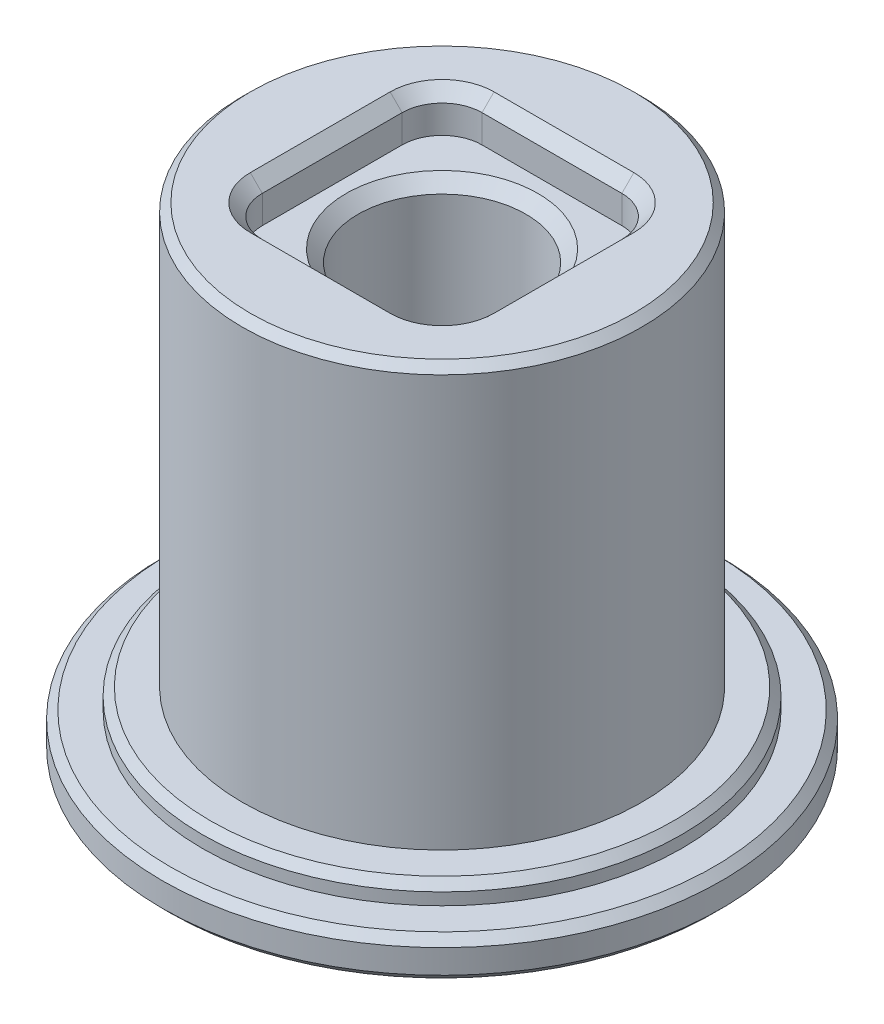
SolidWorks part; units mm, degrees
material "보통 탄소강"
ref_plane "정면" through (0, 0, 0) normal (0, 0, 1) x (1, 0, 0)
ref_plane "윗면" through (0, 0, 0) normal (0, 1, 0) x (1, 0, 0)
ref_plane "우측면" through (0, 0, 0) normal (1, 0, 0) x (0, 0, -1)
sketch "스케치1" plane through (0, 0, 0) normal (0, 1, 0) x (1, 0, 0)
  line L1 (-2.75, -2.75) -> (2.75, -2.75)
  line L2 (-2.75, -2.75) -> (-2.75, 2.75)
  line L3 (-2.75, 2.75) -> (2.75, 2.75)
  line L4 (2.75, -2.75) -> (2.75, 2.75)
  line L5 (-2.75, -2.75) -> (2.75, 2.75) construction
  line L6 (-2.75, 2.75) -> (2.75, -2.75) construction
  circle A0 centre (0, 0) radius 7
  circle A1 centre (0, 0) radius 6
  circle A2 centre (0, 0) radius 5
  circle A3 centre (0, 0) radius 4.25
  circle A5 centre (0, 0) radius 2.1
  dimension "D1" = 14
  dimension "D2" = 12
  dimension "D3" = 10
  dimension "D4" = 8.5
  dimension "D5" = 5.5
  dimension "D6" = 4.2
  dimension "D7" = 5.5
extrude "보스-돌출1" add sketch "스케치1" along normal blind 1 contours A0 A1 region at (-6.802, 0, 0)
extrude "보스-돌출2" add sketch "스케치1<4>" along normal blind 1.5 contours A1 A2 region at (-5.8303, 0, 0)
sketch "스케치1<4>" plane through (0, 0, 0) normal (0, 1, 0) x (1, 0, 0) same geometry as "스케치1"
extrude "보스-돌출3" add sketch "스케치1<5>" along normal blind 12 contours A2 A3 region at (-4.8586, 0, 0)
sketch "스케치1<5>" plane through (0, 0, 0) normal (0, 1, 0) x (1, 0, 0) same geometry as "스케치1"
extrude "보스-돌출4" add sketch "스케치1<6>" along normal blind 7 from offset 5 contours A3 region at (-4.1298, 0, 0)
sketch "스케치1<6>" plane through (0, 0, 0) normal (0, 1, 0) x (1, 0, 0) same geometry as "스케치1"
extrude "보스-돌출5" add sketch "스케치1<7>" along normal blind 6 from offset 5 contours A5 region at (-2.6722, 0, 0)
sketch "스케치1<7>" plane through (0, 0, 0) normal (0, 1, 0) x (1, 0, 0) same geometry as "스케치1"
fillet "필렛1" radius 1 4 edges at (2.75, 11.5, 2.75) (-2.75, 11.5, 2.75) (2.75, 11.5, -2.75) (-2.75, 11.5, -2.75)
chamfer "모따기1" distance 0.2 angle 45 4 edges at (0, 12, 5) (0, 1, 7) (0, 0, 7) (0, 1.5, 6)
chamfer "모따기2" distance 0.3 angle 45 1 edges at (0, 0, 4.25)
chamfer "모따기3" distance 0.3 angle 45 9 edges at (0, 11, 2.1) (0, 12, 2.75) (2.75, 12, 0) (-2.75, 12, 0) (0, 12, -2.75) (-2.4571, 12, 2.4571) (2.4571, 12, 2.4571) (-2.4571, 12, -2.4571) (2.4571, 12, -2.4571)
